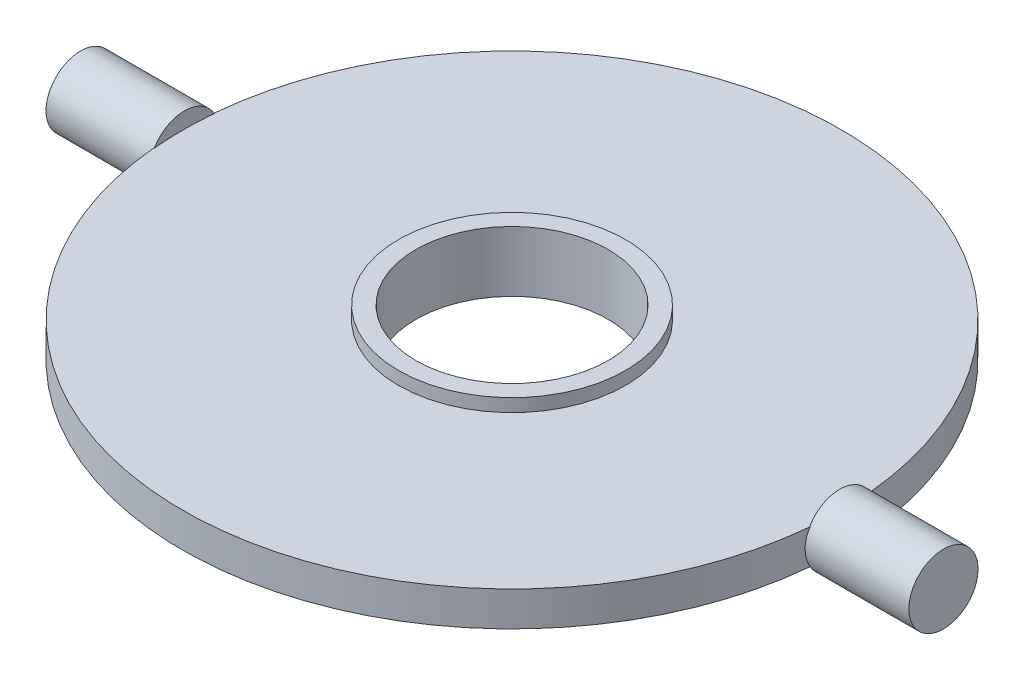
SolidWorks part; units mm, degrees
ref_plane "Front Plane" through (0, 0, 0) normal (0, 0, 1) x (1, 0, 0)
ref_plane "Top Plane" through (0, 0, 0) normal (0, 1, 0) x (1, 0, 0)
ref_plane "Right Plane" through (0, 0, 0) normal (1, 0, 0) x (0, 0, -1)
sketch "Sketch1" plane through (0, 0, 0) normal (0, 1, 0) x (1, 0, 0)
  line L0 (-76.4354, 0) -> (76.4354, 0) construction
  line L1 (-49.8894, 4) -> (-49.8894, -4)
  line L2 (0, 38.1) -> (0, -38.1) construction
  line L3 (-49.8894, 4) -> (-37.8894, 4)
  line L4 (-49.8894, -4) -> (-37.8894, -4)
  line L5 (49.8894, -4) -> (37.8894, -4)
  line L6 (49.8894, 4) -> (49.8894, -4)
  line L7 (49.8894, 4) -> (37.8894, 4)
  line L8 (-49.8894, 0) -> (-38.1, 0)
  line L9 (49.8894, 0) -> (38.1, 0)
  circle A0 centre (0, 0) radius 38.1
  circle A1 centre (0, 0) radius 11.125
  circle A2 centre (0, 0) radius 13.125
  point P6 (0, 0)
  point P9 (-49.8894, 0)
  dimension "D1" = 76.2
  dimension "D4" = 22.25
  dimension "D2" = 8
  dimension "D3" = 12
  dimension "D5" = 2
extrude "Boss-Extrude1" add sketch "Sketch1" along normal mid plane 4 contours A0 L1 region at (0, 0, -37.0224)
revolve "Revolve1" add sketch "Sketch1<6>" angle 360 about L0 region at (-43.9595, 0, 2.0059) region at (43.9595, 0, 2.0059)
sketch "Sketch1<6>" plane through (0, 0, 0) normal (0, 1, 0) x (1, 0, 0) same geometry as "Sketch1"
extrude "Boss-Extrude2" add sketch "Sketch1<7>" along normal mid plane 7 contours A2 A1 region at (-12.7538, 0, 0)
sketch "Sketch1<7>" plane through (0, 0, 0) normal (0, 1, 0) x (1, 0, 0) same geometry as "Sketch1"
